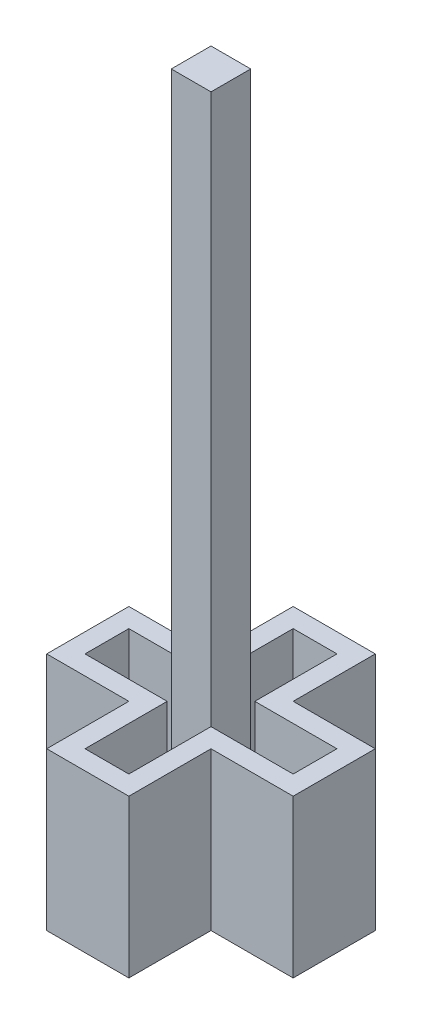
SolidWorks part; units mm, degrees
ref_plane "Front Plane" through (0, 0, 0) normal (0, 0, 1) x (1, 0, 0)
ref_plane "Top Plane" through (0, 0, 0) normal (0, 1, 0) x (1, 0, 0)
ref_plane "Right Plane" through (0, 0, 0) normal (1, 0, 0) x (0, 0, -1)
sketch "Sketch1" plane through (0, 0, 0) normal (0, 1, 0) x (1, 0, 0)
  line L0 (-3, 3) -> (-3, 9)
  line L1 (-3, 9) -> (3, 9)
  line L2 (3, 9) -> (3, 3)
  line L3 (3, 3) -> (9, 3)
  line L4 (9, 3) -> (9, -3)
  line L5 (9, -3) -> (3, -3)
  line L6 (3, -3) -> (3, -9)
  line L7 (3, -9) -> (-3, -9)
  line L8 (-3, -9) -> (-3, -3)
  line L9 (-3, -3) -> (-9, -3)
  line L10 (-9, -3) -> (-9, 3)
  line L11 (-9, 3) -> (-3, 3)
  point P13 (-9, 0)
  point P14 (0, 9)
  dimension "D1" = 6
  dimension "D2" = 6
extrude "Boss-Extrude1" add sketch "Sketch1" along normal blind 1.5
sketch "Sketch3" plane through (0, 1.5, 0) normal (0, 1, 0) x (1, 0, 0)
  line L0 (-1.6, 1.6) -> (-7.6, 1.6)
  line L1 (-7.6, 1.6) -> (-7.6, -1.6)
  line L2 (-7.6, -1.6) -> (-1.6, -1.6)
  line L3 (-1.6, -1.6) -> (-1.6, -7.6)
  line L4 (-1.6, -7.6) -> (1.6, -7.6)
  line L5 (1.6, -7.6) -> (1.6, -1.6)
  line L6 (1.6, -1.6) -> (7.6, -1.6)
  line L7 (7.6, -1.6) -> (7.6, 1.6)
  line L8 (7.6, 1.6) -> (1.6, 1.6)
  line L9 (1.6, 1.6) -> (1.6, 7.6)
  line L10 (1.6, 7.6) -> (-1.6, 7.6)
  line L11 (-1.6, 7.6) -> (-1.6, 1.6)
  line L12 (-3, 3) -> (-9, 3)
  line L13 (-9, 3) -> (-9, -3)
  line L14 (-9, -3) -> (-3, -3)
  line L15 (-3, -3) -> (-3, -9)
  line L16 (-3, -9) -> (3, -9)
  line L17 (3, -9) -> (3, -3)
  line L18 (3, -3) -> (9, -3)
  line L19 (9, -3) -> (9, 3)
  line L20 (9, 3) -> (3, 3)
  line L21 (3, 3) -> (3, 9)
  line L22 (3, 9) -> (-3, 9)
  line L23 (-3, 9) -> (-3, 3)
  line L24 (-3, 3) -> (-9, 3)
  line L25 (-9, 3) -> (-9, -3)
  line L26 (-9, -3) -> (-3, -3)
  line L27 (-3, -3) -> (-3, -9)
  line L28 (-3, -9) -> (3, -9)
  line L29 (3, -9) -> (3, -3)
  line L30 (3, -3) -> (9, -3)
  line L31 (9, -3) -> (9, 3)
  line L32 (9, 3) -> (3, 3)
  line L33 (3, 3) -> (3, 9)
  line L34 (3, 9) -> (-3, 9)
  line L35 (-3, 9) -> (-3, 3)
  dimension "D2" = 1.4
extrude "Boss-Extrude5" add sketch "Sketch3" along normal blind 10
sketch "Sketch2" plane through (0, 1.5, 0) normal (0, 1, 0) x (1, 0, 0)
  line L1 (-1.45, 1.45) -> (1.45, 1.45)
  line L2 (-1.45, 1.45) -> (-1.45, -1.45)
  line L3 (-1.45, -1.45) -> (1.45, -1.45)
  line L4 (1.45, 1.45) -> (1.45, -1.45)
  point P4 (-1.45, 0)
  point P5 (0, 1.45)
  dimension "D1" = 2.9
extrude "Boss-Extrude2" add sketch "Sketch2" along normal blind 10
sketch "Sketch4" [suppressed] plane through (0, 12, 0) normal (0, 1, 0) x (1, 0, 0)
  line L1 (-11.5, 3.5) -> (-3.5, 3.5)
  line L2 (-11.5, 3.5) -> (-11.5, -3.5)
  line L3 (-11.5, -3.5) -> (-3.5, -3.5)
  line L4 (-3.5, 3.5) -> (-3.5, -3.5)
extrude "Cut-Extrude1" [suppressed] cut sketch "Sketch4" against normal through all
sketch "Sketch5" [suppressed] plane through (0, 12, 0) normal (0, 1, 0) x (1, 0, 0)
  line L0 (-1.4, 1.4) -> (-1.4, -1.4) construction
  line L1 (-3.5, 1.7) -> (-1.7, 1.7)
  line L2 (-3.5, 1.7) -> (-3.5, -1.7)
  line L3 (-3.5, -1.7) -> (-1.7, -1.7)
  line L4 (-1.7, 1.7) -> (-1.7, 1.4)
  line L5 (-1.4, 1.4) -> (-1.7, 1.4)
  line L6 (-1.4, 1.4) -> (-1.4, -1.4)
  line L7 (-1.4, -1.4) -> (-1.7, -1.4)
  line L9 (1.4, 1.4) -> (-1.4, 1.4) construction
  line L10 (-1.4, -1.4) -> (1.4, -1.4) construction
  line L11 (-1.7, -1.4) -> (-1.7, -1.7)
extrude "Boss-Extrude6" [suppressed] add sketch "Sketch5" against normal blind 10
sketch "Sketch6" [suppressed] plane through (0, 12, 0) normal (0, 1, 0) x (1, 0, 0)
  line L1 (-3.5, 11.5) -> (3.5, 11.5)
  line L2 (-3.5, 11.5) -> (-3.5, 3.5)
  line L3 (-3.5, 3.5) -> (3.5, 3.5)
  line L4 (3.5, 11.5) -> (3.5, 3.5)
extrude "Cut-Extrude2" [suppressed] cut sketch "Sketch6" against normal through all
sketch "Sketch7" [suppressed] plane through (0, 12, 0) normal (0, 1, 0) x (1, 0, 0)
  line L0 (1.4, 1.4) -> (-1.7, 1.4) construction
  line L1 (-1.7, 3.5) -> (-1.7, 1.4) construction
  line L2 (-1.7, 3.5) -> (1.7, 3.5) construction
  line L3 (1.4, 1.4) -> (-1.7, 1.4)
  line L4 (-1.7, 3.5) -> (-1.7, 1.4)
  line L5 (-1.7, 3.5) -> (1.7, 3.5)
  line L8 (1.7, 3.5) -> (1.7, 1.7)
  line L9 (1.7, 1.7) -> (1.4, 1.7)
  line L10 (1.4, 1.7) -> (1.4, 1.4)
extrude "Boss-Extrude7" [suppressed] add sketch "Sketch7" against normal blind 10
sketch "Sketch8" [suppressed] plane through (0, 12, 0) normal (0, 1, 0) x (1, 0, 0)
  line L1 (3.5, 3.5) -> (11.5, 3.5)
  line L2 (3.5, 3.5) -> (3.5, -3.5)
  line L3 (3.5, -3.5) -> (11.5, -3.5)
  line L4 (11.5, 3.5) -> (11.5, -3.5)
extrude "Cut-Extrude3" [suppressed] cut sketch "Sketch8" against normal through all
sketch "Sketch9" [suppressed] plane through (0, 12, 0) normal (0, 1, 0) x (1, 0, 0)
  line L0 (1.4, -1.4) -> (1.4, 1.4) construction
  line L1 (3.5, 1.7) -> (1.7, 1.7) construction
  line L2 (3.5, 1.7) -> (3.5, -1.7) construction
  line L3 (1.7, -1.7) -> (3.5, -1.7) construction
  line L4 (1.4, -1.4) -> (1.4, 1.4)
  line L5 (3.5, 1.7) -> (1.7, 1.7)
  line L6 (3.5, 1.7) -> (3.5, -1.7)
  line L7 (1.7, -1.7) -> (3.5, -1.7)
  line L8 (1.4, 1.4) -> (1.7, 1.4)
  line L9 (1.7, 1.4) -> (1.7, 1.7)
  line L10 (1.4, -1.4) -> (1.7, -1.4)
  line L11 (1.7, -1.4) -> (1.7, -1.7)
extrude "Boss-Extrude8" [suppressed] add sketch "Sketch9" against normal blind 10
sketch "Sketch10" plane through (0, 11.5, 0) normal (0, 1, 0) x (1, 0, 0)
  line L4 (-1.45, 1.45) -> (-1.45, -1.45)
  line L6 (-1.45, 1.45) -> (-1.45, -1.45)
  line L12 (-1.45, -1.45) -> (1.45, -1.45)
  line L14 (-1.45, -1.45) -> (1.45, -1.45)
  line L15 (1.45, -1.45) -> (1.45, 1.45)
  line L16 (1.45, -1.45) -> (1.45, 1.45)
  line L18 (1.45, 1.45) -> (-1.45, 1.45)
  line L19 (1.45, 1.45) -> (-1.45, 1.45)
  dimension "D1" = 0
extrude "Boss-Extrude9" add sketch "Sketch10" along normal blind 40
sketch "Sketch11" [suppressed] plane through (0, 11.5, 0) normal (0, 1, 0) x (1, 0, 0)
  line L0 (-3, 9) -> (-3, -9) construction
  line L5 (1.45, 1.45) -> (-3, 1.45)
  line L6 (1.45, 1.45) -> (1.45, -1.45)
  line L7 (1.45, -1.45) -> (-3, -1.45)
  line L8 (-3, 1.45) -> (-3, -1.45)
  line L9 (-1.6, -1.45) -> (1.6, -1.45) construction
extrude "Boss-Extrude10" [suppressed] add sketch "Sketch11" along normal blind 40
sketch "Sketch12" [suppressed] plane through (0, 11.5, 0) normal (0, 1, 0) x (1, 0, 0)
  line L0 (-1.6, -1.45) -> (1.45, -1.45) construction
  line L1 (1.45, -1.45) -> (-3, -1.45)
  line L2 (1.45, -1.45) -> (1.45, 3)
  line L3 (1.45, 3) -> (-3, 3)
  line L4 (-3, -1.45) -> (-3, 3)
  line L5 (1.45, -1.45) -> (1.45, 1.6) construction
extrude "Boss-Extrude11" [suppressed] add sketch "Sketch12" along normal blind 40
sketch "Sketch13" [suppressed] plane through (0, 11.5, 0) normal (0, 1, 0) x (1, 0, 0)
  line L0 (-3, 9) -> (-3, -9) construction
  line L1 (-3, 1.45) -> (3, 1.45)
  line L2 (-3, 1.45) -> (-3, -1.45)
  line L3 (-3, -1.45) -> (3, -1.45)
  line L4 (3, 1.45) -> (3, -1.45)
  line L5 (3, -9) -> (3, 9) construction
  line L7 (1.6, 1.45) -> (-1.6, 1.45) construction
  line L8 (-1.6, -1.45) -> (1.6, -1.45) construction
extrude "Boss-Extrude12" [suppressed] add sketch "Sketch13" along normal blind 40
equation "\"mdfWidth\"= 3"
equation "\"cellSide\"= 180"
equation "\"mazeHeight\" = 50"
equation "\"slitHeight\"= 10"
equation "\"gripWidth\"= 6"
equation "\"wallThickness\"= 1.5"
equation "\"slitWidth\" = \"wallThickness\""
equation "\"D1@Sketch1\"= \"mdfWidth\" + 2 * \"wallThickness\""
equation "\"D2@Sketch1\"=\"gripWidth\""
equation "\"D1@Boss-Extrude1\"= \"wallThickness\""
equation "\"D1@Boss-Extrude2\"= \"slitHeight\""
equation "\"D2@Sketch3\"=\"wallThickness\" - \"jeu\""
equation "\"D1@Boss-Extrude5\"= \"slitHeight\""
equation "\"jeu\"= 0.1"
equation "\"D1@Sketch2\"=\"mdfWidth\"- \"jeu\""
equation "\"D1@Boss-Extrude6\"= \"slitHeight\""
equation "\"D1@Boss-Extrude7\"= \"slitHeight\""
equation "\"D1@Boss-Extrude8\"= \"slitHeight\""
equation "\"D1@Boss-Extrude9\"= \"mazeHeight\" - \"slitHeight\""
equation "\"D1@Boss-Extrude10\"= \"mazeHeight\" - \"slitHeight\""
equation "\"D1@Boss-Extrude11\"= \"mazeHeight\" - \"slitHeight\""
equation "\"D1@Boss-Extrude12\"= \"mazeHeight\" - \"slitHeight\""
